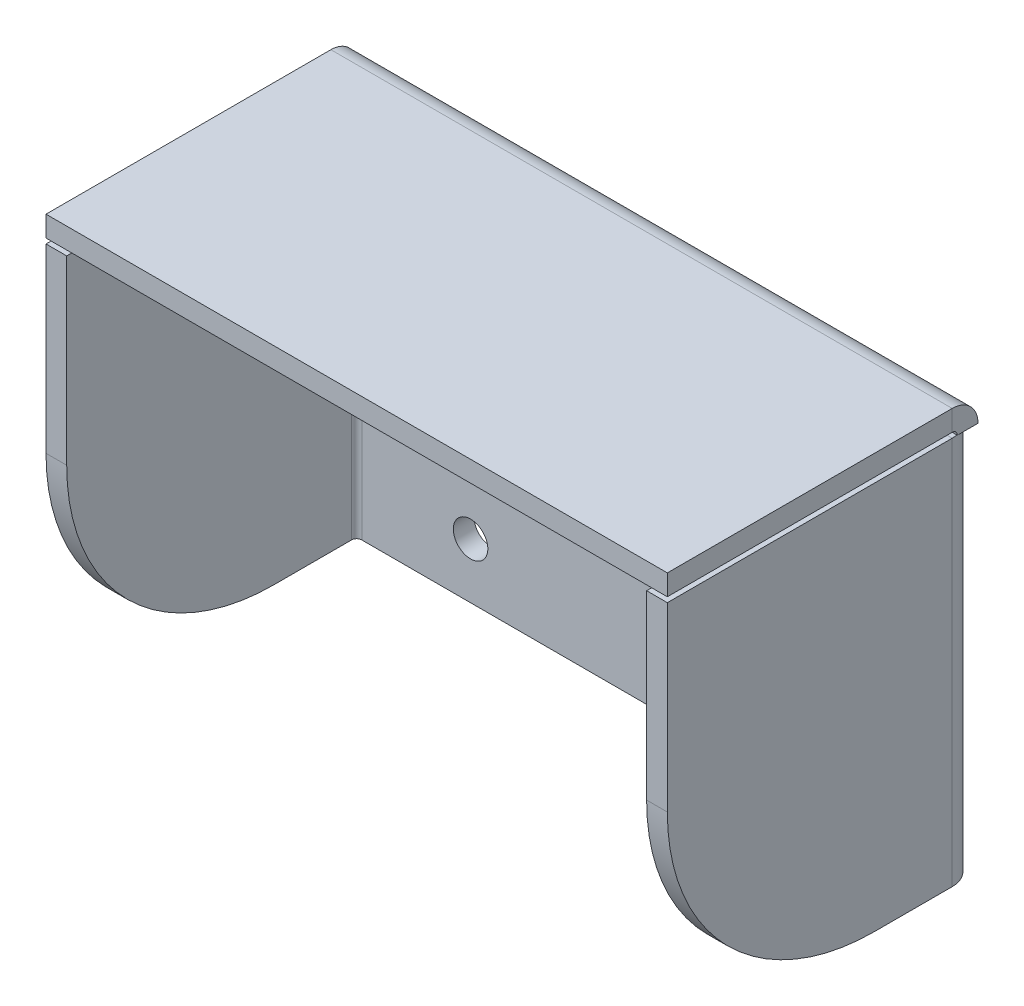
SolidWorks part; units mm, degrees
note: The reader was unsure of these and kept them because the rebuilt part matched: thickness of "基体-法兰1", "边线-法兰1", "边线-法兰2", "钣金6", "钣金7", "钣金8", "钣金9"; flange length of "边线-法兰1", "边线-法兰2".
ref_plane "前视基准面" through (0, 0, 0) normal (0, 0, 1) x (1, 0, 0)
ref_plane "上视基准面" through (0, 0, 0) normal (0, 1, 0) x (1, 0, 0)
ref_plane "右视基准面" through (0, 0, 0) normal (1, 0, 0) x (0, 0, -1)
sketch "草图2" plane through (0, 0, 0) normal (0, 0, 1) x (1, 0, 0)
  line L1 (-45, -30) -> (45, -30)
  line L2 (-45, -30) -> (-45, 30)
  line L3 (-45, 30) -> (45, 30)
  line L4 (45, -30) -> (45, 30)
  line L5 (-45, -30) -> (45, 30) construction
  line L6 (-45, 30) -> (45, -30) construction
  point P0 (0, 0)
  dimension "D1" = 60
  dimension "D2" = 90
base flange "基体-法兰1" sketch "草图2" thickness 3 reverse thickness direction no parameters "D1"=0.7366
edge flange "边线-法兰1" sketch "草图9" flange angle 90 flange length 45 flange position material inside bend radius 0.7366 thickness 3 relief rectangular parameters "D6"=10
sketch "草图9" plane through (0, 30, 0) normal (0, 1, 0) x (-1, 0, 0)
  line L0 (-45, 0) -> (45, 0) construction
  line L1 (-45, 0) -> (45, 0)
  line L2 (-45, 0) -> (-45, 42)
  line L3 (-45, 42) -> (45, 42)
  line L4 (45, 42) -> (45, 0)
bend "边线折弯1" bend radius 0.7366 bend angle 90 parameters "D5"=1
edge flange "边线-法兰2" sketch "草图14" flange profiles "草图14", "草图15" flange angle 90 flange length 45 flange position material inside bend radius 0.7366 thickness 3 relief none parameters "D6"=10, "D8"=1
sketch "草图14" plane through (-45, 0, 0) normal (-1, 0, 0) x (0, -1, 0)
  line L2 (-26.2634, 0) -> (-26.2634, 42)
  line L3 (-26.2634, 42) -> (30, 42)
  line L4 (30, 42) -> (30, 0)
  line L5 (-26.2634, 0) -> (30, 0) construction
  line L6 (-26.2634, 0) -> (30, 0)
sketch "草图15" plane through (45, 0, 0) normal (1, 0, 0) x (0, 1, 0)
  line L2 (-30, 0) -> (-30, 42)
  line L3 (-30, 42) -> (26.2634, 42)
  line L4 (26.2634, 42) -> (26.2634, 0)
  line L5 (-30, 0) -> (26.2634, 0) construction
  line L6 (-30, 0) -> (26.2634, 0)
bend "边线折弯2" bend radius 0.7366 bend angle 90 parameters "D5"=2
bend "边线折弯3" bend radius 0.7366 bend angle 90 parameters "D5"=3
sketch "草图16" plane through (0, 0, -3) normal (0, 0, -1) x (-1, 0, 0)
  point P0 (25.5, -22)
  point P1 (25.5, 14)
  point P3 (-25.5, 14)
  point P5 (-25.5, -22)
hole_wizard "M6 螺纹孔1" positions "草图17" profile "草图18" tap size "M6" standard "ISO" end condition through all
sketch "草图17" plane through (0, 0, -3) normal (0, 0, -1) x (-1, 0, 0)
  point P0 (-25.5, 14)
  point P3 (-25.5, -22)
  point P6 (25.5, -22)
  point P9 (25.5, 14)
sketch "草图18" plane through (25.5, 14, -3) normal (1, 0, 0) x (0, 1, 0)
  line L0 (0, 0) -> (0, 45)
  line L1 (0, 45) -> (2.5, 45)
  line L2 (2.5, 45) -> (2.5, 0)
  line L5 (2.5, 0) -> (0, 0)
  line L11 (0, -6.35) -> (0, 107.95) construction
  dimension "通孔螺纹孔钻头直径" = 5
  dimension "通孔螺纹孔钻头深度" = 45
cosmetic thread "孔螺蚊线1"
cosmetic thread "孔螺蚊线2"
cosmetic thread "孔螺蚊线3"
cosmetic thread "孔螺蚊线4"
fillet "圆角1" radius 30 2 edges at (43.5, -30, 42) (-43.5, -30, 42)
sketch "折弯-线1" plane through (0, 0, 0) normal (0, 1, 0) x (1, 0, 0)
sketch "边界框1" plane through (0, 0, 0) normal (0, 1, 0) x (1, 0, 0)
sheet metal parameters "钣金6" thickness 3 parameters "D1"=0.7366, "D7"=2
flat pattern "平板型式6" [suppressed]
sketch "折弯-线2" plane through (0, 0, 0) normal (0, 1, 0) x (1, 0, 0)
sketch "边界框2" [suppressed] plane through (0, 0, 0) normal (0, 1, 0) x (1, 0, 0)
sheet metal parameters "钣金7" thickness 3 parameters "D1"=0.7366, "D7"=2
flat pattern "平板型式6" [suppressed]
sketch "折弯-线2" plane through (0, 0, 0) normal (0, 1, 0) x (1, 0, 0)
sketch "边界框2" [suppressed] plane through (0, 0, 0) normal (0, 1, 0) x (1, 0, 0)
bend of the flat pattern "展开-<边线折弯1>1"
sheet metal parameters "钣金8" thickness 3 parameters "D1"=0.7366, "D7"=2
flat pattern "平板型式6" [suppressed]
sketch "折弯-线2" plane through (0, 0, 0) normal (0, 1, 0) x (1, 0, 0)
sketch "边界框2" [suppressed] plane through (0, 0, 0) normal (0, 1, 0) x (1, 0, 0)
bend of the flat pattern "展开-<边线折弯1>1"
bend of the flat pattern "展开-<边线折弯2>1"
bend of the flat pattern "展开-<边线折弯3>1"
sheet metal parameters "钣金9" thickness 3 parameters "D1"=0.7366, "D7"=2
flat pattern "平板型式6" [suppressed]
sketch "折弯-线2" plane through (0, 0, 0) normal (0, 1, 0) x (1, 0, 0)
sketch "边界框2" [suppressed] plane through (0, 0, 0) normal (0, 1, 0) x (1, 0, 0)
bend of the flat pattern "展开-<边线折弯1>1"
bend of the flat pattern "展开-<边线折弯2>1"
bend of the flat pattern "展开-<边线折弯3>1"
